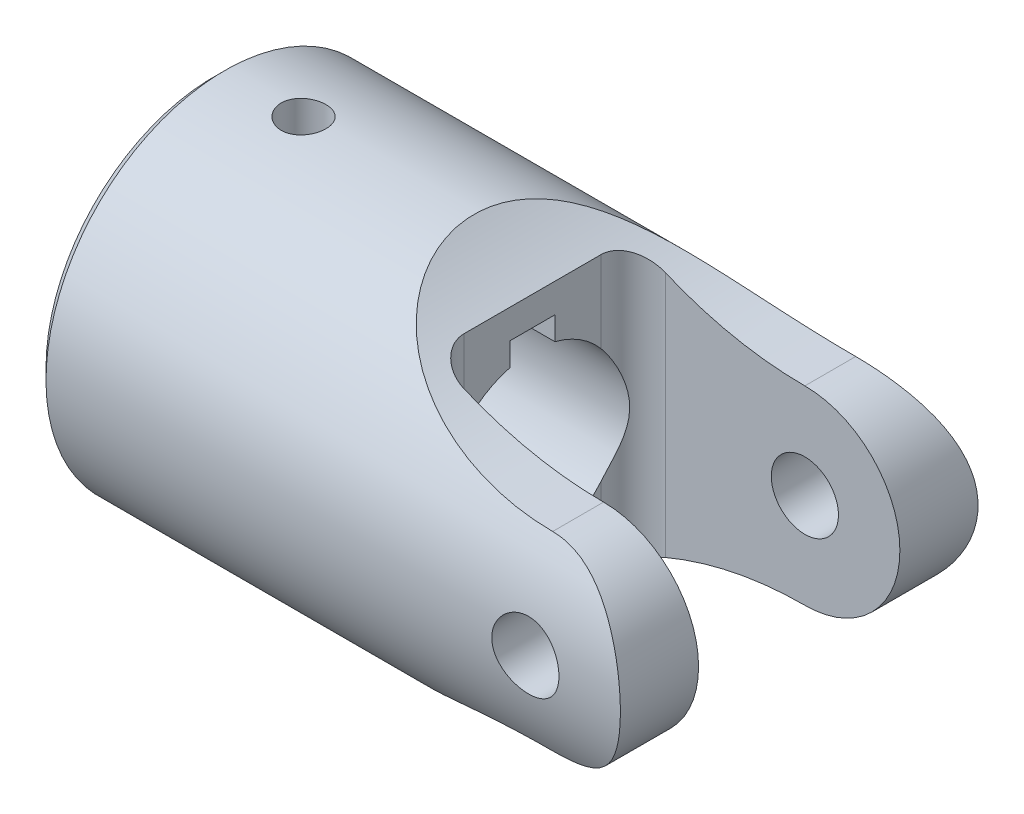
SolidWorks part; units mm, degrees
material "SAE 1145"
ref_plane "Front Plane" through (0, 0, 0) normal (0, 0, 1) x (1, 0, 0)
ref_plane "Top Plane" through (0, 0, 0) normal (0, 1, 0) x (1, 0, 0)
ref_plane "Right Plane" through (0, 0, 0) normal (1, 0, 0) x (0, 0, -1)
sketch "Sketch1" plane through (0, 0, 0) normal (1, 0, 0) x (0, 0, -1)
  circle A0 centre (0, 0) radius 25.4
  dimension "D1" = 50.8
extrude "Boss-Extrude1" add sketch "Sketch1" along normal blind 83.0898
sketch "Sketch4" plane through (0, 0, 0) normal (0, 0, 1) x (1, 0, 0)
  line L0 (0, 0) -> (100.3708, 0) construction
  line L1 (0, 25.4) -> (0, -25.4) construction
  line L2 (83.0898, -25.4) -> (83.0898, 25.4)
  line L3 (83.0898, -25.4) -> (83.0898, 25.4) construction
  line L4 (0, -25.4) -> (83.0898, -25.4) construction
  line L5 (36.917, -25.4) -> (83.0898, -25.4)
  line L6 (83.0898, 25.4) -> (0, 25.4) construction
  line L7 (36.917, 25.4) -> (83.0898, 25.4)
  arc A0 (69.596, 13.4937) -> (69.596, -13.4937) centre (69.596, 0) cw
  arc A1 (69.596, -13.4937) -> (36.917, -25.4) centre (69.596, -64.2938) ccw
  arc A2 (69.596, 13.4937) -> (36.917, 25.4) centre (69.596, 64.2938) cw
  dimension "D1" = 13.4937
  dimension "D2" = 50.8
  dimension "D3" = 50.8
extrude "Cut-Extrude1" cut sketch "Sketch4" against normal mid plane 87.376 contours A2 A0 L2 L7 | A0 A1 L5 L2 region at (65.6767, -19.3456, 0) region at (65.6767, 19.3456, 0)
sketch "Sketch5" plane through (0, 0, 0) normal (0, 0, 1) x (1, 0, 0)
  circle A0 centre (69.596, 0) radius 4.7689
  dimension "D1" = 9.5377
extrude "Cut-Extrude2" cut sketch "Sketch5" against normal mid plane 87.376
sketch "Sketch6" plane through (0, 0, 0) normal (0, 1, 0) x (1, 0, 0)
  line L0 (69.596, 32.1437) -> (69.596, -33.5748)
  line L1 (83.0898, -14.2938) -> (83.0898, 14.2939)
  line L2 (83.0898, -25.4) -> (83.0898, 25.4) construction
  line L3 (83.0898, 14.2939) -> (49.784, 14.2938)
  line L4 (45.212, 9.7218) -> (45.212, -9.7218)
  line L5 (49.784, -14.2938) -> (83.0898, -14.2938)
  line L6 (0, 0) -> (97.1359, 0) construction
  arc A0 (49.784, 14.2938) -> (45.212, 9.7218) centre (49.784, 9.7218) ccw
  arc A1 (45.212, -9.7218) -> (49.784, -14.2938) centre (49.784, -9.7218) ccw
  point P15 (45.212, 0)
  dimension "D2" = 4.572
  dimension "D3" = 4.572
  dimension "D1" = 24.384
  dimension "D4" = 28.5877
extrude "Cut-Extrude3" cut sketch "Sketch6" against normal mid plane 87.376 contours L4 L6 L0 L3 A0 | L6 L4 A1 L5 L0 | L6 L0 L5 L1 | L0 L6 L1 L3 region at (76.3429, 0, -7.1469) region at (57.5496, 0, -7.0671) region at (76.3429, 0, 7.1469) region at (57.5496, 0, 7.0671)
sketch "Sketch7" plane through (45.212, 0, 0) normal (1, 0, 0) x (0, 0, -1)
  line L0 (-3.175, 12.2967) -> (-3.175, 15.5956)
  line L1 (-3.175, 15.5956) -> (3.175, 15.5956)
  line L2 (3.175, 15.5956) -> (3.175, 12.2967)
  line L3 (0, 0) -> (0, 24.0388) construction
  arc A0 (-3.175, 12.2967) -> (3.175, 12.2967) centre (0, 0) ccw
  point P5 (0, 15.5956)
  dimension "D1" = 25.4
  dimension "D3" = 28.2956
  dimension "D2" = 6.35
extrude "Cut-Extrude4" cut sketch "Sketch7" against normal through all and the other way blind 87.376
chamfer "Chamfer1" distance 1.524 angle 45 1 edges at (0, 0, -25.4)
sketch "Sketch9" plane through (0, 0, 0) normal (0, 1, 0) x (1, 0, 0)
  line L0 (0, 23.876) -> (0, -23.876) construction
  circle A0 centre (12.7, 0) radius 3.175
  dimension "D2" = 6.35
  dimension "D1" = 12.7
extrude "Cut-Extrude5" cut sketch "Sketch9" along normal through all
